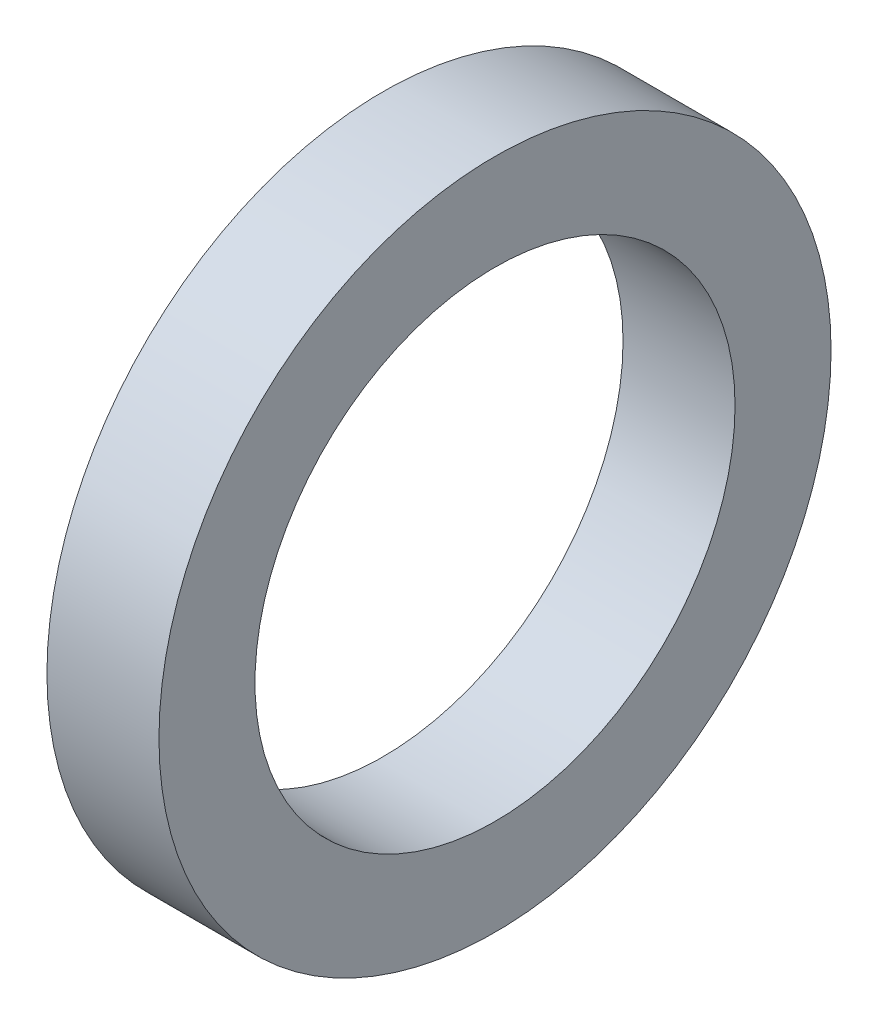
SolidWorks part; units mm, degrees
material "1023 Carbon Steel Sheet (SS)"
ref_plane "Front Plane" through (0, 0, 0) normal (0, 0, 1) x (1, 0, 0)
ref_plane "Top Plane" through (0, 0, 0) normal (0, 1, 0) x (1, 0, 0)
ref_plane "Right Plane" through (0, 0, 0) normal (1, 0, 0) x (0, 0, -1)
sketch "Sketch1" plane through (0, 0, 0) normal (1, 0, 0) x (0, 0, -1)
  circle A0 centre (0, 0) radius 21
  circle A1 centre (0, 0) radius 15
  dimension "D1" = 30
  dimension "D2" = 42
extrude "Boss-Extrude1" add sketch "Sketch1" along normal mid plane 7
ref_axis "Axis1" through (-3.85, 0, 0) along (1, 0, 0)
